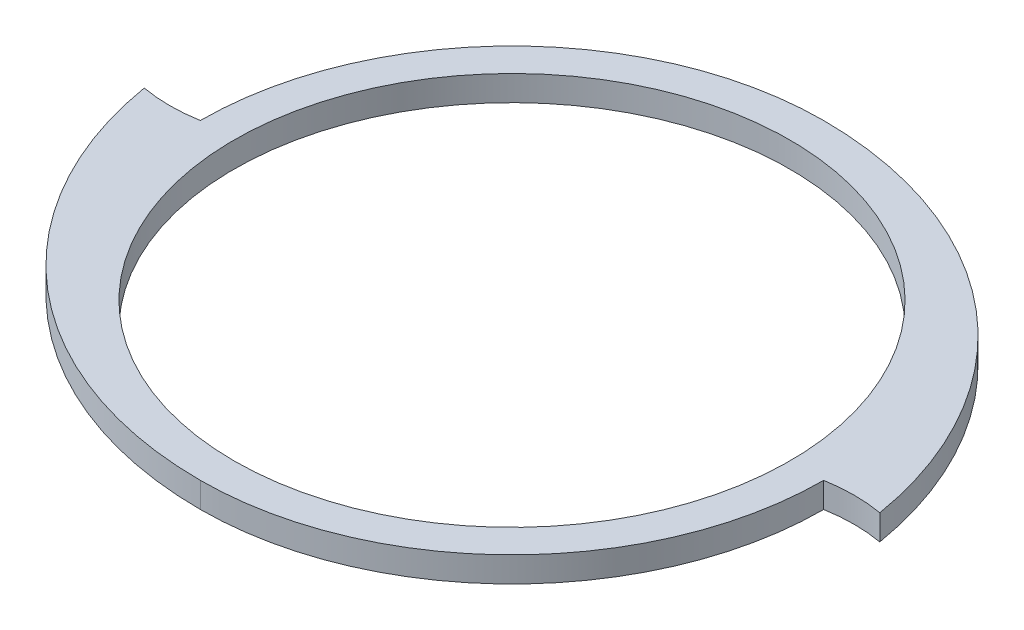
SolidWorks part; units mm, degrees
material "Alloy Steel"
ref_plane "Front Plane" through (0, 0, 0) normal (0, 0, 1) x (1, 0, 0)
ref_plane "Top Plane" through (0, 0, 0) normal (0, 1, 0) x (1, 0, 0)
ref_plane "Right Plane" through (0, 0, 0) normal (1, 0, 0) x (0, 0, -1)
sketch "Sketch1" plane through (0, 0, 0) normal (0, 1, 0) x (1, 0, 0)
  line L0 (0, 0) -> (-131, 0) construction
  line L1 (-131.0158, 0.1809) -> (-133.7819, 31.7972) construction
  line L2 (-133.0207, 0.3563) -> (-165.8378, 6.1428) construction
  line L3 (-131, 0) -> (-131, 32.0934) construction
  line L4 (-129.3938, 0) -> (-182.8754, 0) construction
  line L5 (-111, 0) -> (-131, 0) construction
  circle A0 centre (0, 0) radius 99
  arc A7 (0, -111) -> (-111, 0) centre (0, 0) ccw
  arc A8 (-131, 0) -> (0, -111) centre (0, 21.8018) ccw
  arc A9 (-131, 0) -> (-111, 0) centre (-121, 56.7128) ccw
  dimension "D1" = 198
  dimension "D2" = 12
  dimension "D3" = 10
  dimension "D4" = 5
  dimension "D5" = 20
extrude "Boss-Extrude1" add sketch "Sketch1" along normal mid plane 9
pattern_circular "CirPattern1" count 2 over 360 about axis through (0, 4.5, 0) along (0, -1, 0) of "Boss-Extrude1" reverse direction yes
equation "\"ring_id\"=198"
equation "\"D1@Sketch1\"=\"ring_id\""
